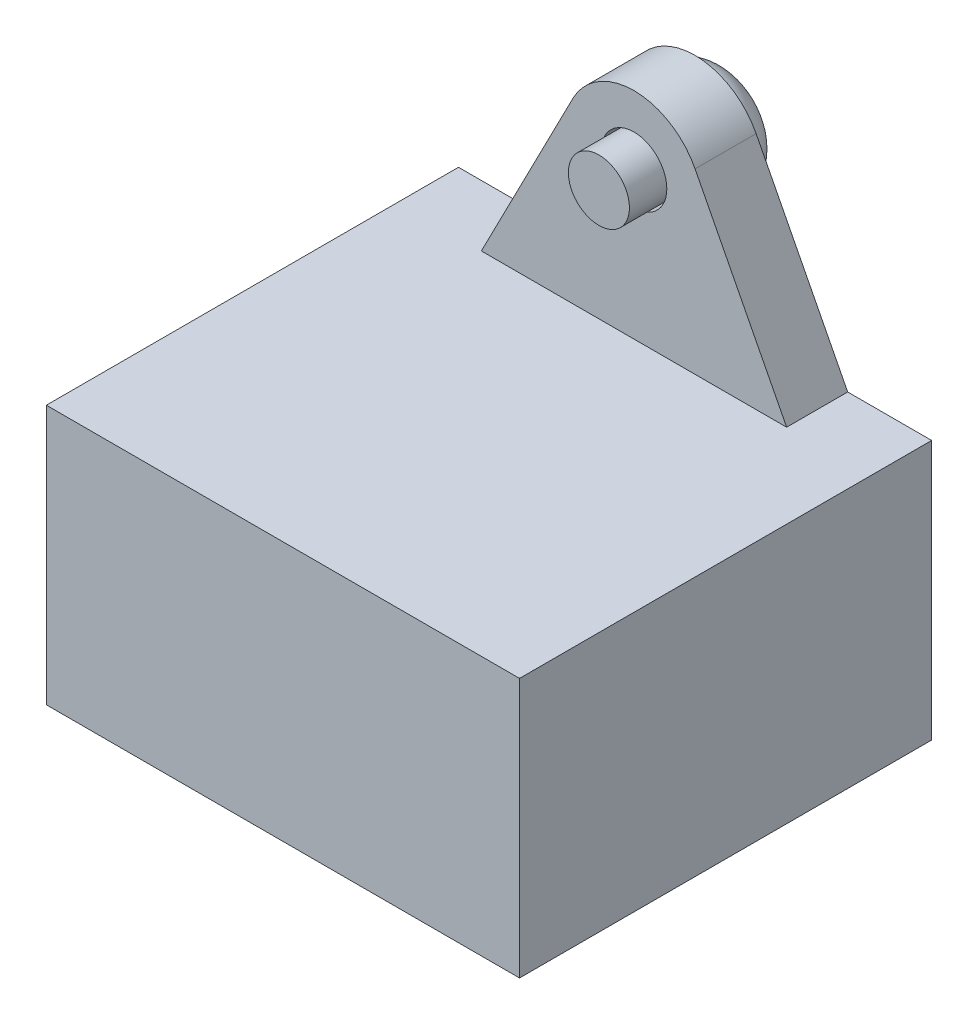
SolidWorks part; units mm, degrees
ref_plane "Front Plane" through (0, 0, 0) normal (0, 0, 1) x (1, 0, 0)
ref_plane "Top Plane" through (0, 0, 0) normal (0, 1, 0) x (1, 0, 0)
ref_plane "Right Plane" through (0, 0, 0) normal (1, 0, 0) x (0, 0, -1)
ref_plane "Plane1" through (0, 0, -4) normal (0, 0, 1) x (1, 0, 0)
sketch "Sketch1" plane through (0, 0, -4) normal (0, 0, 1) x (1, 0, 0)
  line L0 (-10, -9.6) -> (10, -9.6)
  line L1 (10, -9.6) -> (4.0014, 2.0588)
  line L2 (-4.0014, 2.0588) -> (-10, -9.6)
  line L3 (0, -9.6) -> (0, 4.5) construction
  line L4 (-10, -26.6) -> (10, -26.6) construction
  line L5 (-10, 4.5) -> (10, 4.5) construction
  line L6 (16.06, 0) -> (-16.06, 0) construction
  arc A0 (4.0014, 2.0588) -> (-4.0014, 2.0588) centre (0, 0) ccw
  dimension "KSS_2" = 20
  dimension "MSM_21" = 31.1
  dimension "MSM_22" = 4.5
  dimension "MSM_23" = 17
extrude "Boss-Extrude1" add sketch "Sketch1" along normal blind 4
sketch "Sketch2" plane through (0, 0, -4) normal (0, 0, 1) x (1, 0, 0)
  line L0 (0, 0) -> (0, -26.6) construction
  line L1 (-15.5, -9.6) -> (15.5, -9.6)
  line L2 (-15.5, -9.6) -> (-15.5, -26.6)
  line L3 (-15.5, -26.6) -> (15.5, -26.6)
  line L4 (15.5, -9.6) -> (15.5, -26.6)
  line L5 (-10, -9.6) -> (10, -9.6) construction
  line L6 (-10, -26.6) -> (10, -26.6) construction
  dimension "MSM_25" = 31
extrude "Boss-Extrude2" add sketch "Sketch2" along normal blind 27
sketch "Sketch3" plane through (0, 0, 0) normal (0, 0, 1) x (1, 0, 0)
  line L0 (0, 5.4) -> (0, -9.6) construction
  line L1 (-10, 5.4) -> (10, 5.4)
  line L2 (-10, 5.4) -> (-10, -9.6)
  line L3 (-10, -9.6) -> (10, -9.6)
  line L4 (10, 5.4) -> (10, -9.6)
  line L5 (-10, -9.6) -> (10, -9.6) construction
  dimension "FIX_1" = 15
extrude "Boss-Extrude3" [suppressed] add sketch "Sketch3" along normal blind 4
sketch "Sketch4" plane through (0, 0, 0) normal (0, 0, 1) x (1, 0, 0)
  circle A0 centre (0, 0) radius 2.15
  dimension "MSM_57" = 4.3
extrude "Cut-Extrude1" cut sketch "Sketch4" against normal through all
sketch "Sketch5" plane through (0, 0, 0) normal (1, 0, 0) x (0, 0, -1)
  line L0 (-2.3, 0) -> (6.2, 0) construction
  line L2 (-2.3, 0) -> (6.2, 0)
  line L3 (-2.3, 2) -> (-2.3, 0)
  line L4 (6.2, 1.6) -> (6.2, 0)
  line L5 (4, 3.8) -> (4, 2)
  line L6 (4, 2) -> (-2.3, 2)
  line L8 (16.775, 0) -> (-16.775, 0) construction
  line L9 (4, 14.575) -> (4, -14.575) construction
  arc A0 (6.2, 1.6) -> (4, 3.8) centre (4, 1.6) ccw
  dimension "FIX_6" = 7.6
  dimension "FIX_4" = 2.2
  dimension "FIX_5" = 6.3
  dimension "FIX_3" = 4
revolve "Revolve1" add sketch "Sketch5" angle 360 about L0
cosmetic thread "Thread1" parameters "ATD"=3.242
sketch "Sketch6" plane through (0, 0, -6.2) normal (0, 0, 1) x (1, 0, 0)
  line L0 (0, -16.06) -> (0, 16.06) construction
  line L1 (0, 1.4434) -> (-1.25, 0.7217)
  line L2 (-1.25, 0.7217) -> (-1.25, -0.7217)
  line L3 (-1.25, -0.7217) -> (0, -1.4434)
  line L4 (0, -1.4434) -> (1.25, -0.7217)
  line L5 (1.25, -0.7217) -> (1.25, 0.7217)
  line L6 (1.25, 0.7217) -> (0, 1.4434)
  circle A0 centre (0, 0) radius 1.25 construction
  dimension "FIX_8" = 2.5
extrude "Cut-Extrude2" cut sketch "Sketch6" along normal blind 1.3
sketch "Sketch7" plane through (0, 0, 23) normal (0, 0, 1) x (1, 0, 0)
  line L0 (-15.5, -18.1) -> (15.5, -18.1) construction
  line L1 (-18.25, -13.35) -> (18.25, -13.35)
  line L2 (-18.25, -13.35) -> (-18.25, -22.85)
  line L3 (-18.25, -22.85) -> (18.25, -22.85)
  line L4 (18.25, -13.35) -> (18.25, -22.85)
  line L6 (-15.5, -9.6) -> (-15.5, -26.6) construction
  line L7 (0, 0) -> (0, -26.6) construction
  line L9 (-18.25, -13.35) -> (18.25, -22.85) construction
  line L10 (-18.25, -22.85) -> (18.25, -13.35) construction
  point P0 (0, -18.1)
  dimension "KSS_4" = 9.5
  dimension "KSS_5" = 36.5
extrude "Cut-Extrude3" [suppressed] cut sketch "Sketch7" against normal blind 1
fillet "Fillet1" [suppressed] radius 1
fillet "Fillet2" [suppressed] radius 0.5
ref_plane "FRAME CENTER" through (0, 0, 33.5) normal (0, 0, 1) x (1, 0, 0)
ref_axis "ROTATION AXIS" through (0, -21.625, 33.5) along (0, 1, 0)
equation "\"B\"= 30"
equation "\"Cut-Extrude3\"  = iif ( \"KSS_2@Sketch1\" < > 20 , \"unsuppressed\" , \"suppressed\" )"
equation "\"Fillet1\"  = iif ( \"KSS_2@Sketch1\" < > 20 , \"unsuppressed\" , \"suppressed\" )"
equation "\"Fillet2\" = iif ( \"KSS_2@Sketch1\" < > 20 , \"unsuppressed\" , \"suppressed\" )"
equation "\"KSS_1@FRAME CENTER\"= ( ( \"B\" + 25 ) / 2 ) + 6"
equation "\"KSS_3@Boss-Extrude1\"= iif ( \"KSS_2@Sketch1\" < > 20 , 5 , 4 )"
equation "\"KSS_4@Sketch7\" = iif ( \"MSM_21@Sketch1\" = 21.5 , 9.5 , iif ( \"MSM_21@Sketch1\" = 25.7 , 14 , 9.5 ) )"
equation "\"KSS_5@Sketch7\" = iif ( \"MSM_21@Sketch1\" = 21.5 , 36.5 , iif ( \"MSM_21@Sketch1\" = 25.7 , 37 , 36.5 ) )"
equation "\"KSS_2@Sketch1\"= iif ( \"MSM_21@Sketch1\" = 21.5 , 16 , iif ( \"MSM_21@Sketch1\" = 25.7 , 15 , iif ( \"MSM_21@Sketch1\" = 28.2 , 15 , iif ( \"MSM_21@Sketch1\" = 27.25 , 17 , iif ( \"MSM_21@Sketch1\" = 31.1 , 20 , 20 ) ) ) ) )"
